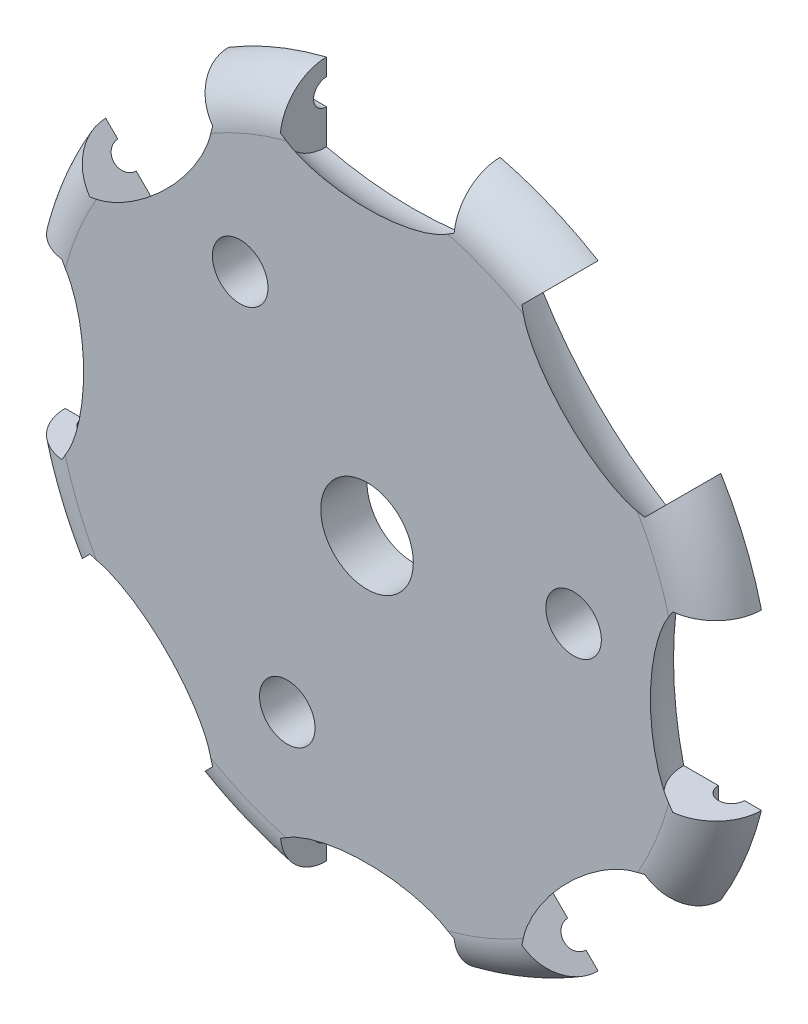
SolidWorks part; units mm, degrees
ref_plane "Front Plane" through (0, 0, 0) normal (0, 0, 1) x (1, 0, 0)
ref_plane "Top Plane" through (0, 0, 0) normal (0, 1, 0) x (1, 0, 0)
ref_plane "Right Plane" through (0, 0, 0) normal (1, 0, 0) x (0, 0, -1)
sketch "Sketch1" plane through (0, 0, 0) normal (0, 0, 1) x (1, 0, 0)
  circle A0 centre (0, 0) radius 24.6062
  dimension "D1" = 49.2125
extrude "Boss-Extrude1" add sketch "Sketch1" along normal blind 3.175
fillet "Fillet1" radius 3.1852 1 edges at (24.6063, 0, 3.175)
sketch "Sketch2" plane through (0, 0, 3.175) normal (0, 0, 1) x (1, 0, 0)
  line L0 (0, 0) -> (-9.4164, -22.7332) construction
  line L1 (0, 0) -> (0, -6.9354) construction
  circle A0 centre (-5.4676, -13.1999) radius 1.905
  circle A1 centre (-8.6977, 11.335) radius 1.905
  circle A2 centre (14.1653, 1.8649) radius 1.905
  circle A3 centre (0, 0) radius 3.175
  circle A4 centre (0, 0) radius 24.6063 construction
  point P9 (0, 0)
  dimension "D2" = 3.81
  dimension "D4" = 6.35
  dimension "D1" = 14.2875
  dimension "D5" = 22.5
  dimension "D3" = 3
extrude "Cut-Extrude1" cut sketch "Sketch2" against normal through all
sketch "Sketch5" plane through (0, 0, 0) normal (0, 0, 1) x (1, 0, 0)
  line L0 (-5.9531, 21.8122) -> (5.9531, 21.8122)
  line L1 (5.9531, 21.8122) -> (5.9531, 25.0843)
  line L2 (-5.9531, 21.8122) -> (-5.9531, 25.0843)
  line L3 (-5.9531, 21.8122) -> (-8.5086, 21.8122) construction
  arc A0 (-5.9531, 25.0843) -> (5.9531, 25.0843) centre (0, 0) cw
  circle A1 centre (0, 0) radius 24.6063 construction
  point P5 (0, 21.8122)
  point P9 (0, 25.781)
  dimension "D1" = 11.9062
  dimension "D2" = 21.8122
  dimension "D3" = 7.9375
revolve "Cut-Revolve1" cut sketch "Sketch5" angle 360 about L3
sketch "Sketch6" plane through (0, 0, 0) normal (1, 0, 0) x (0, 0, -1)
  line L0 (0, -24.6063) -> (0, 23.8753) construction
  circle A0 centre (0, 21.8122) radius 0.889
  arc A1 (-3.1552, 20.9459) -> (0, 18.5402) centre (0, 21.8122) ccw construction
  dimension "D1" = 1.778
extrude "Cut-Extrude2" cut sketch "Sketch6" against normal mid plane 15.875
pattern_circular "CirPattern1" count 8 over 360 about axis through (0, 0, 0) along (0, 0, 1) of "Cut-Revolve1", "Cut-Extrude2"
